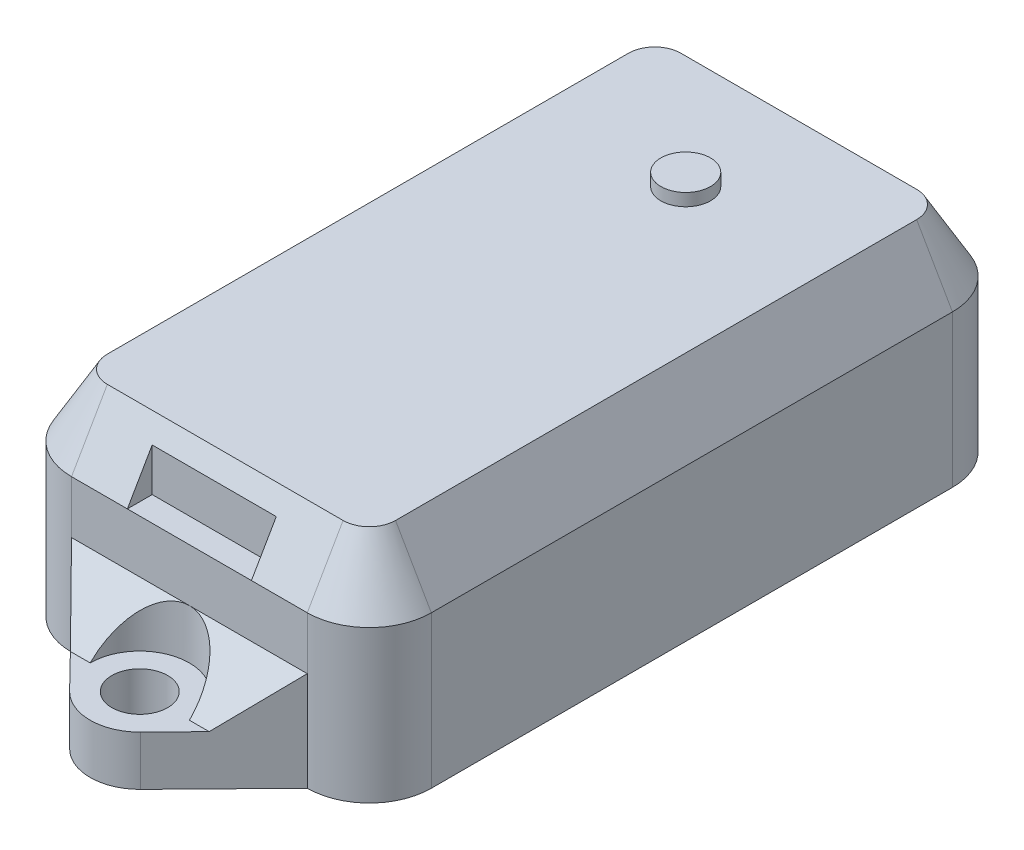
SolidWorks part; units mm, degrees
material "ABS"
ref_plane "Ön Düzlem" through (0, 0, 0) normal (0, 0, 1) x (1, 0, 0)
ref_plane "Üst Düzlem" through (0, 0, 0) normal (0, 1, 0) x (1, 0, 0)
ref_plane "Sağ Düzlem" through (0, 0, 0) normal (1, 0, 0) x (0, 0, -1)
sketch "Çizim1" plane through (0, 0, 0) normal (0, 1, 0) x (1, 0, 0)
  line L0 (0, 5) -> (0, 47)
  line L2 (29, 5) -> (29, 47)
  line L4 (5, 0) -> (11.6388, -6.7953)
  line L5 (24, 0) -> (17.3612, -6.7953)
  line L6 (-28.4942, 26) -> (64.852, 26) construction
  line L7 (5, 52) -> (11.6388, 58.7953)
  line L8 (24, 52) -> (17.3612, 58.7953)
  line L9 (5, 52) -> (24, 52)
  line L10 (5, 0) -> (24, 0)
  arc A2 (24, 0) -> (29, 5) centre (24, 5) ccw
  arc A3 (0, 5) -> (5, 0) centre (5, 5) ccw
  arc A5 (11.6388, -6.7953) -> (17.3612, -6.7953) centre (14.5, -4) ccw
  circle A6 centre (14.5, -4) radius 2.25
  circle A7 centre (14.5, 56) radius 2.25
  arc A8 (0, 47) -> (5, 52) centre (5, 47) cw
  arc A9 (24, 52) -> (29, 47) centre (24, 47) cw
  arc A10 (11.6388, 58.7953) -> (17.3612, 58.7953) centre (14.5, 56) cw
  point P7 (0, 52)
  point P12 (29, 0)
  point P15 (0, 0)
  point P22 (0, 26)
  point P31 (29, 26)
  dimension "D3" = 5
  dimension "D4" = 8
  dimension "D6" = 4.5
  dimension "D8" = 5
  dimension "D13" = 29
  dimension "D1" = 21
  dimension "D2" = 29
  dimension "D5" = 14.5
  dimension "D7" = 26
  dimension "D9" = 6.6388
  dimension "D10" = 9.5
  dimension "D11" = 9.5
  dimension "D12" = 6.6388
extrude "Yükseklik-Ekstrüzyon2" add sketch "Çizim1" along normal blind 17.25 contours L6 L0 A3 L10 A2 L2 | L0 L6 L2 A9 L9 A8 region at (14.5, 0, -13.1715) region at (14.5, 0, -38.8285)
extrude "Yükseklik-Ekstrüzyon3" add sketch "Çizim1<3>" along normal blind 4 contours A10 L7 L9 L8 A7 | L4 A5 L5 L10 A6 region at (14.5, 0, 0.2062) region at (8.4669, 0, -55.2536)
sketch "Çizim1<3>" plane through (0, 0, 0) normal (0, 1, 0) x (1, 0, 0) same geometry as "Çizim1"
chamfer "Pah2" distance 5 angle 30 8 edges at (27.5355, 17.25, -1.4645) (14.5, 17.25, 0) (1.4645, 17.25, -1.4645) (0, 17.25, -26) (1.4645, 17.25, -50.5355) (14.5, 17.25, -52) (27.5355, 17.25, -50.5355) (29, 17.25, -26) first distance on face at (26.4142, 7.7, -1.5858) first distance on face at (14.5, 10.625, 0) first distance on face at (2.5858, 7.7, -1.5858) first distance on face at (0, 8.625, -26) first distance on face at (2.5858, 7.7, -50.4142) first distance on face at (14.5, 10.625, -52) first distance on face at (26.4142, 7.7, -50.4142) first distance on face at (29, 8.625, -26)
sketch "Çizim4" plane through (0, 4, 0) normal (0, 1, 0) x (1, 0, 0)
  line L0 (8.9079, 56) -> (12.25, 56)
  line L1 (5, 52) -> (11.6388, 58.7953) construction
  line L2 (24, 52) -> (17.3612, 58.7953) construction
  line L3 (20.0921, 56) -> (24, 52)
  line L4 (24, 52) -> (5, 52)
  line L5 (5, 52) -> (8.9079, 56)
  line L6 (16.75, 56) -> (20.0921, 56)
  line L7 (2.8868, 26) -> (26.1132, 26) construction
  line L8 (2.8868, 47) -> (2.8868, 5) construction
  line L9 (26.1132, 5) -> (26.1132, 47) construction
  line L10 (5, 0) -> (8.9079, -4)
  line L11 (8.9079, -4) -> (12.25, -4)
  line L12 (16.75, -4) -> (20.0921, -4)
  line L13 (24, 0) -> (5, 0)
  line L14 (20.0921, -4) -> (24, 0)
  arc A0 (12.25, 56) -> (16.75, 56) centre (14.5, 56) ccw
  arc A1 (12.25, -4) -> (16.75, -4) centre (14.5, -4) cw
  dimension "D1" = 2.25
  dimension "D2" = 4
  dimension "D3" = 5.5921
extrude "Yükseklik-Ekstrüzyon4" add sketch "Çizim4" along normal blind 4 contours L5 L0 A0 L6 L3 L4 | L10 L11 A1 L12 L14 L13
sketch "Çizim5" plane through (0, 0, 0) normal (-1, 0, 0) x (0, 0, 1)
  line L6 (-26, 17.25) -> (-26, 0) construction
  line L7 (-47, 17.25) -> (-5, 17.25) construction
  line L8 (-5, 0) -> (-47, 0) construction
  line L9 (0, 8) -> (4, 4)
  line L10 (4, 4) -> (4, 8)
  line L11 (4, 8) -> (0, 8)
extrude "Kes-Ekstrüzyon2" cut sketch "Çizim5" against normal blind 24
sketch "Çizim7" plane through (0, 17.25, 0) normal (0, 1, 0) x (1, 0, 0)
  line L0 (24, 0) -> (5, 0) construction
  line L1 (9.5, 0) -> (19.5, 0)
  line L2 (9.5, 0) -> (9.5, 2)
  line L3 (9.5, 2) -> (19.5, 2)
  line L4 (19.5, 0) -> (19.5, 2)
  dimension "D1" = 2
  dimension "D2" = 10
  dimension "D3" = 4.5
extrude "Kes-Ekstrüzyon3" cut sketch "Çizim7" against normal blind 5
sketch "Çizim8" plane through (0, 17.25, 0) normal (0, 1, 0) x (1, 0, 0)
  circle A0 centre (14.5, 40) radius 2
  dimension "D1" = 4
  dimension "D2" = 40
  dimension "D3" = 14.5
extrude "Yükseklik-Ekstrüzyon6" add sketch "Çizim8" along normal blind 1
sketch "Çizim10" plane through (0, 4, 0) normal (0, 1, 0) x (1, 0, 0)
  circle A0 centre (14.5, 56) radius 4
  dimension "D1" = 8
extrude "Kes-Ekstrüzyon4" cut sketch "Çizim10" along normal blind 10
sketch "Çizim11" plane through (0, 4, 0) normal (0, 1, 0) x (1, 0, 0)
  circle A0 centre (14.5, -4) radius 4
  dimension "D1" = 8
extrude "Kes-Ekstrüzyon5" cut sketch "Çizim11" along normal blind 10
sketch "Çizim12" plane through (0, 0, 0) normal (-1, 0, 0) x (0, 0, 1)
  line L0 (-52, 8) -> (-56, 8)
  line L1 (-56, 8) -> (-56, 4)
  line L2 (-56, 4) -> (-52, 8)
extrude "Kes-Ekstrüzyon6" cut sketch "Çizim12" against normal blind 30
